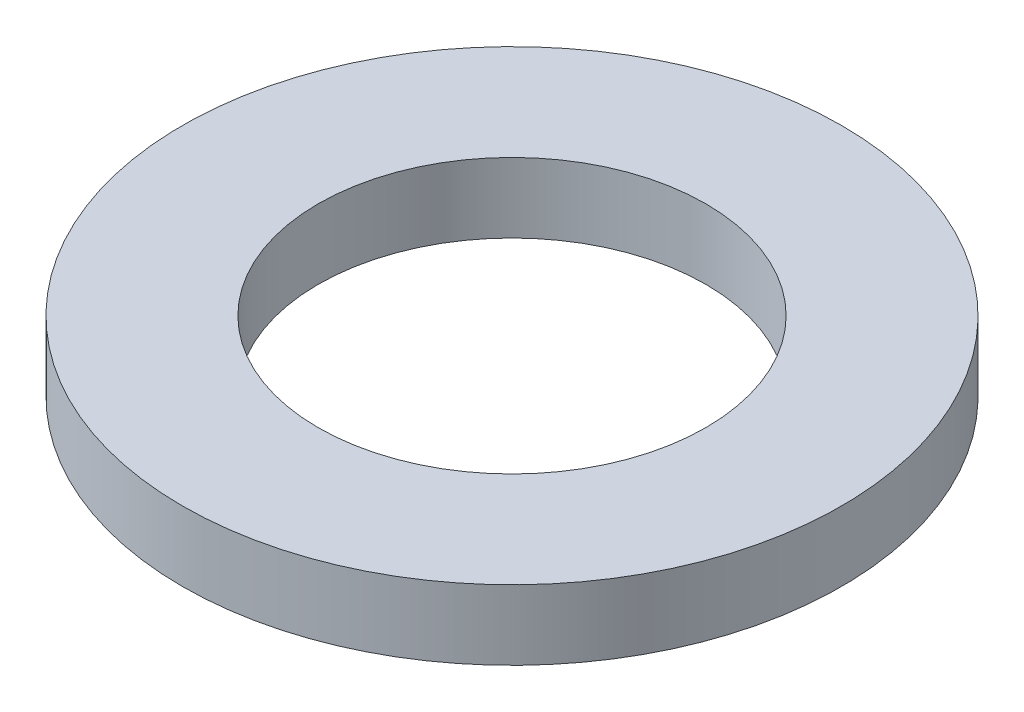
SolidWorks part; units mm, degrees
ref_plane "Front Plane" through (0, 0, 0) normal (0, 0, 1) x (1, 0, 0)
ref_plane "Top Plane" through (0, 0, 0) normal (0, 1, 0) x (1, 0, 0)
ref_plane "Right Plane" through (0, 0, 0) normal (1, 0, 0) x (0, 0, -1)
sketch "Sketch1" plane through (0, 0, 0) normal (0, 1, 0) x (1, 0, 0)
  circle A0 centre (0, 0) radius 85
  dimension "FLANGE_OD" = 170
extrude "Boss-Extrude1" add sketch "Sketch1" along normal blind 18
sketch "Sketch2" plane through (0, 0, 0) normal (0, 1, 0) x (1, 0, 0)
  circle A0 centre (0, 0) radius 50
  dimension "BORE_D" = 100
extrude "Cut-Extrude1" cut sketch "Sketch2" along normal through all
sketch "Sketch3" plane through (0, 18, 0) normal (0, 1, 0) x (1, 0, 0)
  circle A0 centre (0, 0) radius 30.4929 construction
  circle A1 centre (-30.4929, 0) radius 6.2607
  dimension "BOLT_D" = 12.5214
  dimension "BOLT_PCD" = 60.9858
extrude "Cut-Extrude2" cut sketch "Sketch3" against normal blind 15.205 rebuild error yes
pattern_circular "CirPattern1" count 5 over 360 rebuild error yes
